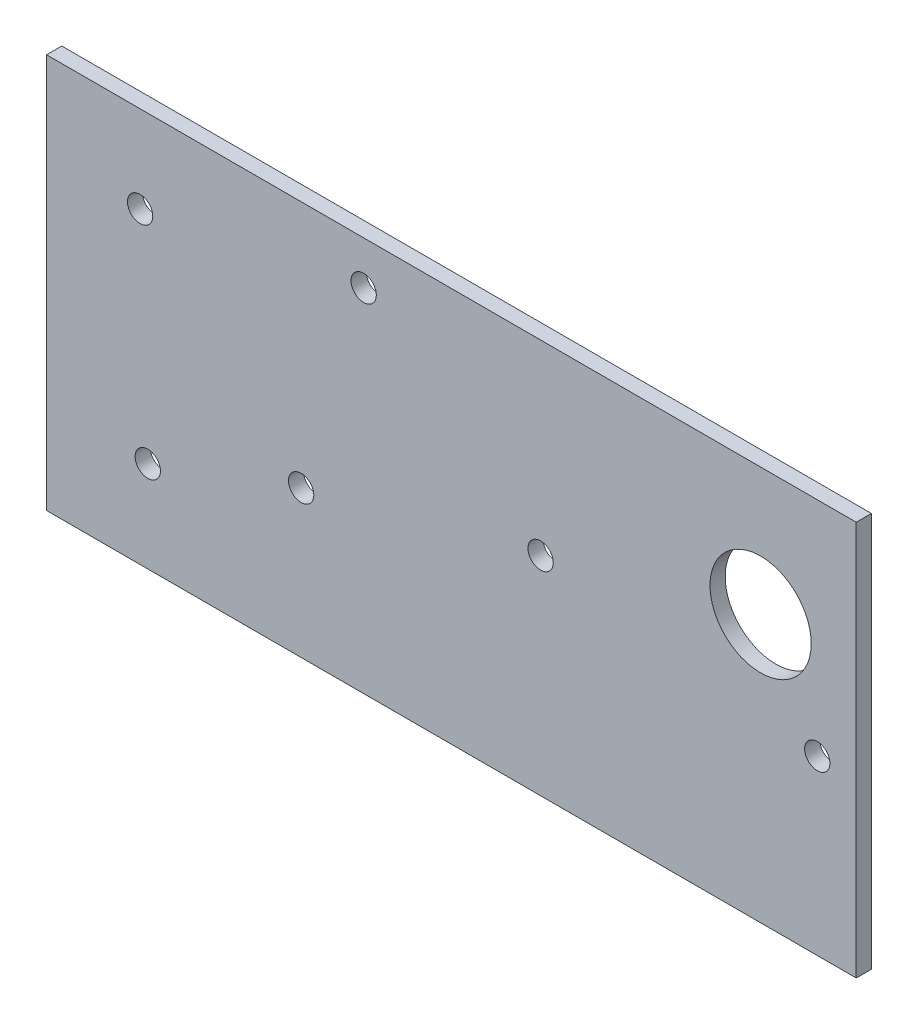
SolidWorks part; units mm, degrees
ref_plane "Front Plane" through (0, 0, 0) normal (0, 0, 1) x (1, 0, 0)
ref_plane "Top Plane" through (0, 0, 0) normal (0, 1, 0) x (1, 0, 0)
ref_plane "Right Plane" through (0, 0, 0) normal (1, 0, 0) x (0, 0, -1)
sketch "Sketch1" plane through (0, 0, 0) normal (0, 0, 1) x (1, 0, 0)
  line L1 (-20, -18) -> (140, -18)
  line L2 (-20, -18) -> (-20, 60)
  line L3 (-20, 60) -> (140, 60)
  line L4 (140, -18) -> (140, 60)
  circle A0 centre (0, 0) radius 2.5
  dimension "D5" = 5
  dimension "D1" = 78
  dimension "D2" = 18
  dimension "D3" = 160
  dimension "D4" = 20
extrude "Boss-Extrude1" add sketch "Sketch1" along normal blind 3
sketch "Sketch2" plane through (0, 0, 3) normal (0, 0, 1) x (1, 0, 0)
  circle A0 centre (121.0967, 34.7638) radius 37.5 construction
  circle A1 centre (42.6585, 51.4364) radius 37.5 construction
  circle A2 centre (-1.5147, 42.85) radius 37.5 construction
  circle A3 centre (121.0967, 34.7638) radius 37.5 construction
  circle A4 centre (42.6585, 51.4364) radius 37.5 construction
  circle A5 centre (-1.5147, 42.85) radius 37.5 construction
  circle A6 centre (30.3051, 11.0301) radius 24.75 construction
  circle A7 centre (30.3051, 11.0301) radius 24.75 construction
  circle A8 centre (77.6301, 23.1169) radius 37.5 construction
  circle A9 centre (132.2988, 16.1204) radius 14.25 construction
  circle A10 centre (77.6301, 23.1169) radius 37.5 construction
  circle A11 centre (132.2988, 16.1204) radius 14.25 construction
  circle A12 centre (-1.5147, 42.85) radius 2.5
  circle A13 centre (30.3051, 11.0301) radius 2.5
  circle A14 centre (42.6585, 51.4364) radius 2.5
  circle A15 centre (77.6301, 23.1169) radius 2.5
  circle A16 centre (121.0967, 34.7638) radius 2.5
  circle A17 centre (132.2988, 16.1204) radius 2.5
  dimension "D1" = 5
  dimension "D2" = 5
extrude "Cut-Extrude1" cut sketch "Sketch2" against normal blind 3
sketch "Sketch3" plane through (0, 0, 3) normal (0, 0, 1) x (1, 0, 0)
  circle A0 centre (121.0967, 34.7638) radius 10
  dimension "D1" = 20
extrude "Cut-Extrude2" cut sketch "Sketch3" against normal blind 3
